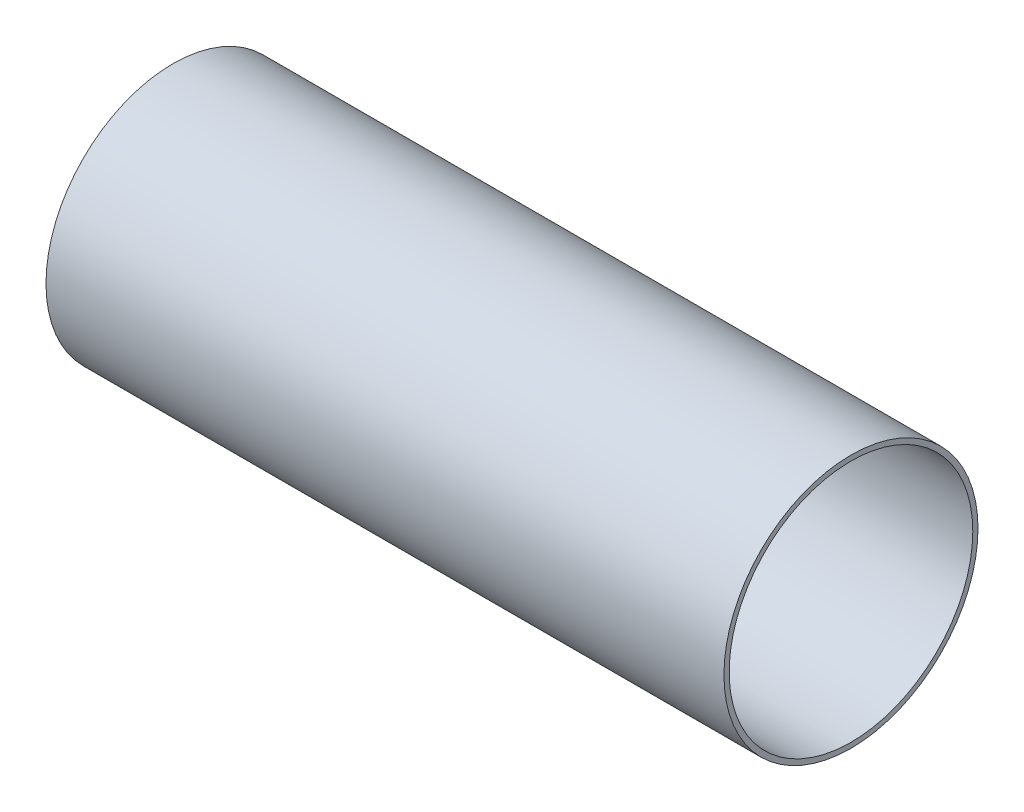
SolidWorks part; units mm, degrees
ref_plane "Front Plane" through (0, 0, 0) normal (1, 0, 0) x (0, 1, 0)
ref_plane "Top Plane" through (0, 0, 0) normal (0, 0, 1) x (0, 1, 0)
ref_plane "Right Plane" through (0, 0, 0) normal (0, 1, 0) x (-1, 0, 0)
sketch "Sketch1" plane through (0, 0, 0) normal (1, 0, 0) x (0, 1, 0)
  circle A0 centre (0, 0) radius 38.0746
  circle A1 centre (0, 0) radius 36.5125
  dimension "D1" = 73.025
  dimension "D2" = 76.1492
extrude "Boss-Extrude1" add sketch "Sketch1" along normal blind 203.2
